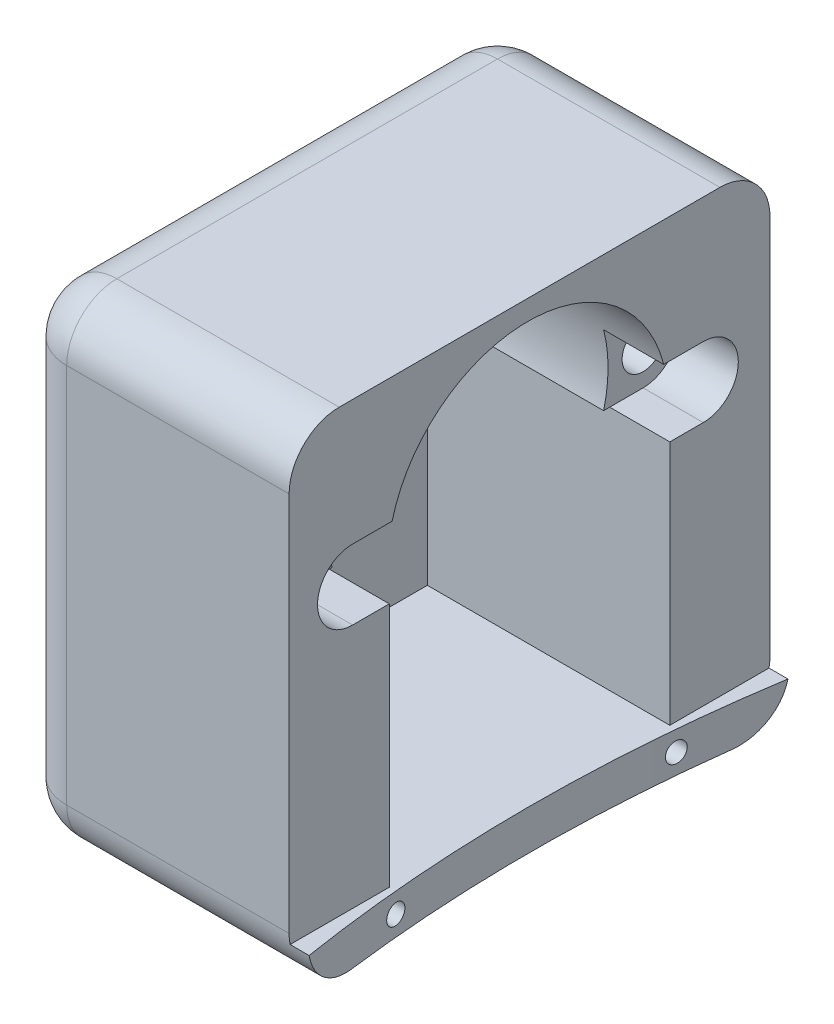
SolidWorks part; units mm, degrees
ref_plane "Plan de face" through (0, 0, 0) normal (0, 0, 1) x (1, 0, 0)
ref_plane "Plan de dessus" through (0, 0, 0) normal (0, 1, 0) x (1, 0, 0)
ref_plane "Plan de droite" through (0, 0, 0) normal (1, 0, 0) x (0, 0, -1)
sketch "Esquisse1" plane through (0, 0, 0) normal (1, 0, 0) x (0, 0, -1)
  line L0 (0, 21) -> (0, -21) construction
  line L1 (-22, -21) -> (22, -21)
  line L2 (-22, -21) -> (-22, 21)
  line L3 (-22, 21) -> (22, 21)
  line L4 (22, -21) -> (22, 21)
  line L5 (-22, -21) -> (22, 21) construction
  line L6 (-22, 21) -> (22, -21) construction
  line L7 (-19.952, 7) -> (-15.562, 7) construction
  line L8 (-17.662, 10.5) -> (-13.7175, 10.5)
  line L9 (-14.162, 7) -> (13.838, 7)
  line L10 (-14, 3.5) -> (-14, -21)
  line L12 (14, 3.5) -> (14, -21)
  line L13 (-17.662, 3.5) -> (-13.7175, 3.5)
  line L14 (17.338, 10.5) -> (13.3934, 10.5)
  line L15 (17.338, 3.5) -> (13.3934, 3.5)
  line L16 (-14.162, 7) -> (19.6279, 7) construction
  line L17 (-24, 23) -> (24, 23)
  line L18 (-24, 23) -> (-24, -25)
  line L19 (-24, -25) -> (24, -25)
  line L20 (24, 23) -> (24, -25)
  line L21 (-14, -23) -> (7.0432, -23) construction
  circle A0 centre (0, 15) radius 3.121
  circle A1 centre (-0.162, 7) radius 14
  circle A2 centre (-17.662, 7) radius 2.1
  circle A3 centre (17.338, 7) radius 2.1
  arc A4 (-17.662, 10.5) -> (-17.662, 3.5) centre (-17.662, 7) ccw
  arc A5 (17.338, 3.5) -> (17.338, 10.5) centre (17.338, 7) ccw
  circle A6 centre (-14, -23) radius 1
  circle A8 centre (14, -23) radius 1
  point P0 (0, 0)
  dimension "D5" = 28
  dimension "D9" = 7
  dimension "D10" = 7
  dimension "D11" = 4.2
  dimension "D12" = 4.2
  dimension "D19" = 2
  dimension "D20" = 2
  dimension "D18" = 2
  dimension "D1" = 44
  dimension "D2" = 42
  dimension "D3" = 6
  dimension "D4" = 8
  dimension "D6" = 17.5
  dimension "D7" = 17.5
  dimension "D8" = 22
  dimension "D13" = 2
  dimension "D14" = 2
  dimension "D15" = 2
  dimension "D16" = 4
  dimension "D17" = 2
  dimension "D21" = 38
  dimension "D22" = 14
  dimension "D23" = 14
  dimension "D24" = 14
  dimension "D25" = 14
extrude "Boss.-Extru.1" add sketch "Esquisse1" against normal blind 27.2 contours L17 L20 L19 L18
sketch "Esquisse2" plane through (0, -25, 0) normal (0, -1, 0) x (1, 0, 0)
  line L0 (-27.2, -24) -> (0, -24) construction
  line L1 (0, 24) -> (1.9067, 24)
  line L3 (0, -24) -> (1.9067, -24)
  line L5 (0, 24) -> (-1.5039, 24)
  line L7 (0, -24) -> (-1.5039, -24)
  line L8 (-1.5039, 24) -> (-1.5039, -24)
  arc A0 (1.9067, 24) -> (1.9067, -24) centre (152, 0) ccw
  dimension "D1" = 304
extrude "Enlèv. mat.-Extru.1" cut sketch "Esquisse1<5>" against normal blind 24.2 contours L9 A1 | L9 A1 A0 | A1 L13 L10 L1 L12 L15 | A0 region at (0, -12.2467, -0.0719) region at (0, 17.8205, -8.2195) region at (0, 1.0582, 0.162) region at (0, 15, 0)
sketch "Esquisse1<5>" plane through (0, 0, 0) normal (1, 0, 0) x (0, 0, -1) same geometry as "Esquisse1"
extrude "Enlèv. mat.-Extru.2" cut sketch "Esquisse1<6>" against normal blind 6 contours L8 A4 L13 A1 A2 | A2 | L15 A5 L14 A1 A3 | A3 region at (0, 3.6022, 15.831) region at (0, 3.6022, -13.6967) region at (0, 7, 17.662) region at (0, 7, -17.338)
sketch "Esquisse1<6>" plane through (0, 0, 0) normal (1, 0, 0) x (0, 0, -1) same geometry as "Esquisse1"
extrude "Enlèv. mat.-Extru.3" cut sketch "Esquisse1<8>" against normal blind 16 contours A2 | A3 region at (0, 7, 17.662) region at (0, 7, -17.338)
sketch "Esquisse1<8>" plane through (0, 0, 0) normal (1, 0, 0) x (0, 0, -1) same geometry as "Esquisse1"
extrude "Boss.-Extru.3" add sketch "Esquisse2" against normal blind 4
extrude "Enlèv. mat.-Extru.4" cut sketch "Esquisse1<9>" against normal blind 10 contours A6 | A8 region at (0, -23, 14) region at (0, -23, -14)
sketch "Esquisse1<9>" plane through (0, 0, 0) normal (1, 0, 0) x (0, 0, -1) same geometry as "Esquisse1"
extrude "Enlèv. mat.-Extru.5" cut sketch "Esquisse1<10>" along normal blind 10 contours A6 | A8 region at (0, -23, 14) region at (0, -23, -14)
sketch "Esquisse1<10>" plane through (0, 0, 0) normal (1, 0, 0) x (0, 0, -1) same geometry as "Esquisse1"
fillet "Congé1" radius 5 8 edges at (-12.6467, -25, 24) (-27.2, -25, 0) (-12.6467, -25, -24) (-27.2, -1, -24) (-13.6, 23, -24) (-27.2, -1, 24) (-27.2, 23, 0) (-13.6, 23, 24)
sketch "Esquisse3" plane through (0, 0, 14) normal (0, 0, -1) x (-1, 0, 0)
  line L0 (0, 3.5) -> (0, -0.0076) construction
  line L1 (6, 3.5) -> (6, 0) construction
  dimension "D1" = 6
